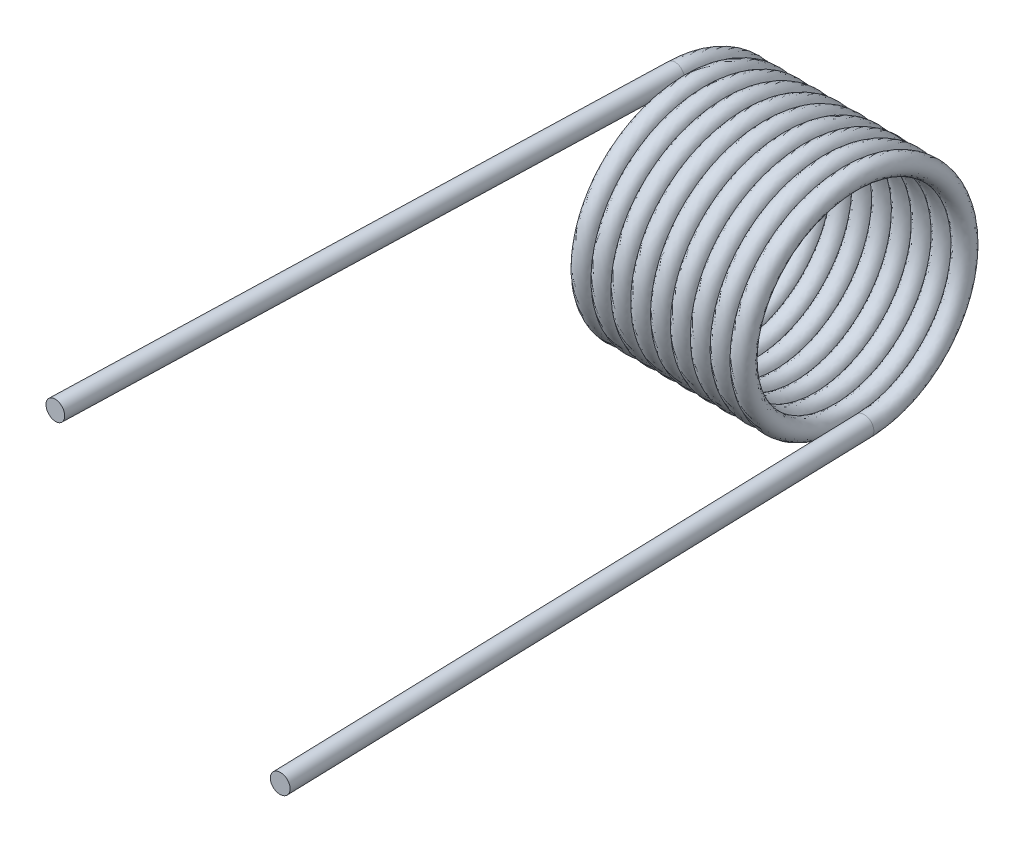
SolidWorks part; units mm, degrees
ref_plane "Front" through (0, 0, 0) normal (0, 0, 1) x (1, 0, 0)
ref_plane "Top" through (0, 0, 0) normal (0, 1, 0) x (1, 0, 0)
ref_plane "Right" through (0, 0, 0) normal (1, 0, 0) x (0, 0, -1)
sketch "Sketch1" plane through (0, 0, 0) normal (1, 0, 0) x (0, 0, -1)
  line L0 (0, 0) -> (0, -4.0386) construction
  line L1 (0, -4.0386) -> (0, -4.445) construction
  line L2 (0, -4.445) -> (0, -4.8514) construction
  circle A0 centre (0, 0) radius 4.0386 construction
  circle A1 centre (0, 0) radius 4.8514 construction
  circle A2 centre (0, 0) radius 4.445
  circle A3 centre (0, -4.445) radius 0.4064 construction
  circle A4 centre (0, 0) radius 3.175 construction
  dimension "Wire Dia" = 0.8128
curve "Helix/Spiral1" pitch 0.8382 height 7.9629 radius 4.445 left hand yes centre (0, 0, 0) axis (1, 0, 0) start towards (0, 1, 0)
ref_plane "Plane1" through (0, 4.445, 0) normal (0.03, 0, -0.9995) x (0.7744, 0.6323, 0.0232)
sketch "Sketch2" plane through (0, 4.445, 0) normal (0.03, 0, -0.9995) x (0.7744, 0.6323, 0.0232)
  circle A0 centre (0, 0) radius 0.4064
  dimension "D1" = 0.8128
sweep "Sweep1" add profiles "Sketch2" path "Helix/Spiral1"
sketch "Sketch3" plane through (0, 0, 0) normal (-0.03, 0, 0.9995) x (-0.7744, -0.6323, -0.0232)
  circle A1 centre (-2.8104, -3.4438) radius 0.4064
  circle A2 centre (-2.8104, -3.4438) radius 0.4064
  dimension "D1" = 0
extrude "Extrude1" add sketch "Sketch3" along normal blind 25.4
sketch "Sketch4" plane through (0.0072, 0, 0.2388) normal (0.03, 0, 0.9995) x (0.8175, -0.5754, -0.0245)
  circle A1 centre (9.0674, 0.944) radius 0.4064
  circle A2 centre (9.0674, 0.944) radius 0.4064
  dimension "D1" = 0
extrude "Extrude2" add sketch "Sketch4" along normal blind 25.4
sketch "Sketch5" plane through (0, 0, 0) normal (1, 0, 0) x (0, 0, -1)
  circle A0 centre (0, 0) radius 3.175 construction
  circle A1 centre (0, 0) radius 3.175
equation "\"D4@Helix/Spiral1\"=\"Wire Dia@Sketch1\"+.001"
equation "\"D1@Sketch2\"=\"Wire Dia@Sketch1\""
equation "\"D1@Extrude2\"=\"Leg Length@Extrude1\""
